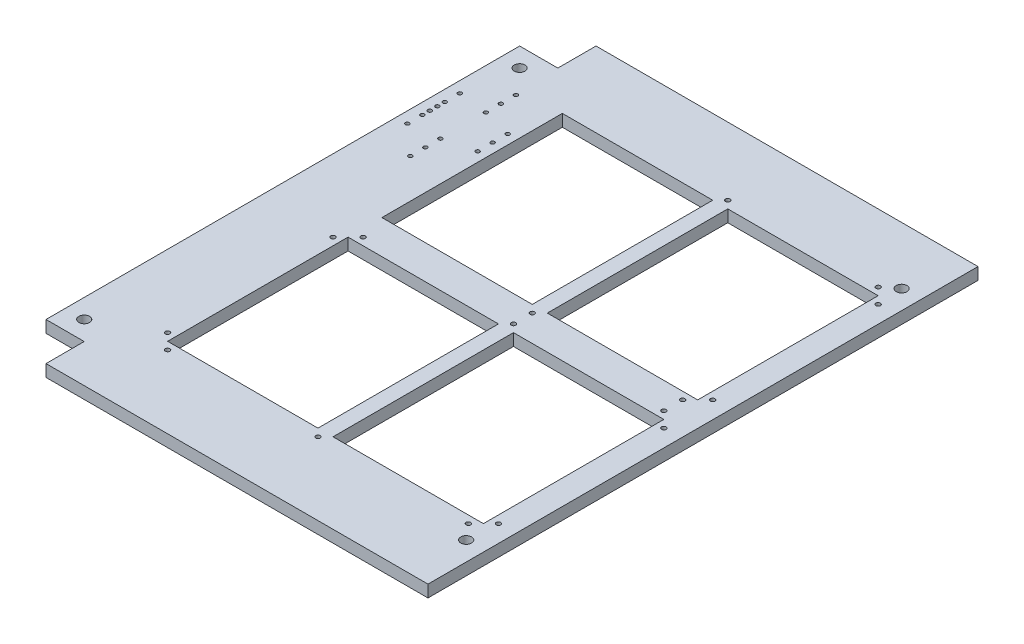
SolidWorks part; units mm, degrees
ref_plane "前视" through (0, 0, 0) normal (0, 0, 1) x (1, 0, 0)
ref_plane "上视" through (0, 0, 0) normal (0, 1, 0) x (1, 0, 0)
ref_plane "右视" through (0, 0, 0) normal (1, 0, 0) x (0, 0, -1)
sketch "Sketch1" plane through (0, 0, 0) normal (0, 1, 0) x (1, 0, 0)
  line L0 (-26.0564, 184.2499) -> (-26.0564, -181.5101) construction
  line L1 (-165.7564, 184.2499) -> (113.6436, 184.2499)
  line L2 (-165.7564, 184.2499) -> (-165.7564, -181.5101)
  line L3 (-165.7564, -181.5101) -> (113.6436, -181.5101)
  line L4 (113.6436, 184.2499) -> (113.6436, -181.5101)
  line L5 (-165.7564, 1.3699) -> (113.6436, 1.3699) construction
  line L6 (-140.3564, -156.1101) -> (-165.7564, -156.1101)
  line L7 (-140.3564, -156.1101) -> (-140.3564, -181.5101)
  line L12 (-140.3564, 158.8499) -> (-140.3564, 184.2499)
  line L13 (-140.3564, 158.8499) -> (-165.7564, 158.8499)
  point P4 (-140.3564, -156.1101)
  point P11 (-140.3564, 158.8499)
  dimension "D1" = 279.4
  dimension "D2" = 365.76
  dimension "D3" = 25.4
  dimension "D4" = 25.4
extrude "Boss-Extrude1" add sketch "Sketch1" along normal blind 8 contours L12 L13 L2 L6 L7 L3 L4 L1 region at (-24.4324, 0, -1.3699)
sketch "Sketch2" plane through (0, 8, 0) normal (0, 1, 0) x (1, 0, 0)
  line L0 (-140.3564, -156.1101) -> (-165.7564, -156.1101) construction
  line L1 (-165.7564, 1.3699) -> (113.6436, 1.3699) construction
  line L2 (-165.7564, 158.8499) -> (-165.7564, -156.1101) construction
  line L3 (113.6436, 184.2499) -> (113.6436, -181.5101) construction
  line L4 (-26.0564, 1.3699) -> (-26.0564, -181.5101) construction
  line L7 (-140.3564, -181.5101) -> (113.6436, -181.5101) construction
  circle A0 centre (-153.0564, -143.3901) radius 3.57
  circle A1 centre (100.9436, 146.1299) radius 3.57
  circle A2 centre (100.9436, -143.3901) radius 3.57
  circle A3 centre (-153.0564, 146.1299) radius 3.57
  point P0 (-153.0564, -143.3901)
  point P1 (-153.0564, -156.1101)
  dimension "D1" = 12.72
extrude "Cut-Extrude1" cut sketch "Sketch2" against normal through all
sketch "Sketch3" plane through (0, 8, 0) normal (0, 1, 0) x (1, 0, 0)
  line L0 (-158.4056, 91.6911) -> (-158.4056, 76.8011) construction
  line L2 (-119.0906, 84.2461) -> (-158.4056, 84.2461) construction
  line L3 (-140.3564, 184.2499) -> (113.6436, 184.2499) construction
  circle A0 centre (-158.4056, 101.6911) radius 1.3
  circle A1 centre (-158.4056, 91.6911) radius 1.3
  circle A2 centre (-158.4056, 86.8011) radius 1.3
  circle A3 centre (-158.4056, 76.8011) radius 1.3
  circle A4 centre (-138.7481, 69.1311) radius 1.3
  circle A5 centre (-138.7481, 59.1311) radius 1.3
  circle A6 centre (-119.0906, 84.2461) radius 1.3
  circle A7 centre (-138.7481, 109.3611) radius 1.3
  circle A8 centre (-119.0906, 94.2461) radius 1.3
  circle A9 centre (-138.7481, 119.3611) radius 1.3
  circle A10 centre (-158.4056, 111.6911) radius 1.3
  circle A11 centre (-158.4056, 96.8011) radius 1.3
  circle A12 centre (-138.7481, 79.1311) radius 1.3
  circle A13 centre (-119.0906, 104.2461) radius 1.3
  circle A14 centre (-138.7481, 129.3611) radius 1.3
  point P0 (-158.4056, 91.6911)
  point P1 (-158.4056, 76.8011)
  dimension "D4" = 3
  dimension "D1" = 14.89
  dimension "D2" = 100.0038
  dimension "D3" = 39.315
extrude "Cut-Extrude2" cut sketch "Sketch3" against normal through all
sketch "Sketch5" plane through (0, 8, 0) normal (0, 1, 0) x (1, 0, 0)
  line L0 (-112.7564, 14.2499) -> (-12.7564, 14.2499)
  line L1 (-112.7564, 134.2499) -> (-12.7564, 134.2499)
  line L2 (-112.7564, 134.2499) -> (-112.7564, -128.2501)
  line L3 (-12.7564, 134.2499) -> (-12.7564, -128.2501)
  line L4 (-165.7564, 158.8499) -> (-165.7564, -156.1101) construction
  line L5 (-112.7564, -8.2501) -> (-12.7564, -8.2501)
  line L6 (-112.7564, -128.2501) -> (-12.7564, -128.2501)
  line L7 (-140.3564, -181.5101) -> (113.6436, -181.5101) construction
  line L8 (-2.7564, 134.2499) -> (-2.7564, -128.2501)
  line L9 (-140.3564, 184.2499) -> (113.6436, 184.2499) construction
  line L10 (97.2436, 134.2499) -> (97.2436, -128.2501)
  line L11 (-2.7564, 134.2499) -> (97.2436, 134.2499)
  line L12 (-2.7564, 14.2499) -> (97.2436, 14.2499)
  line L13 (-2.7564, -8.2501) -> (97.2436, -8.2501)
  line L14 (-2.7564, -128.2501) -> (97.2436, -128.2501)
  dimension "D1" = 100
  dimension "D2" = 53
  dimension "D3" = 120
  dimension "D4" = 22.5
  dimension "D5" = 120
  dimension "D6" = 53.26
  dimension "D7" = 2
  dimension "D8" = 50
extrude "Cut-Extrude3" cut sketch "Sketch5" against normal through all contours L1 L0 | L6 L5 | L8 L12 L10 L11 | L8 L14 L10 L13 region at (-62.7564, 8, -74.2499) region at (-62.7564, 8, 68.2501) region at (47.2436, 8, -74.2499) region at (47.2436, 8, 68.2501)
sketch "Sketch6" plane through (0, 8, 0) normal (0, 1, 0) x (1, 0, 0)
  line L0 (-112.7564, -8.2501) -> (-112.7564, -128.2501) construction
  line L1 (-112.7564, -128.2501) -> (-12.7564, -128.2501) construction
  line L2 (-12.7564, -8.2501) -> (-12.7564, -128.2501) construction
  line L3 (-112.7564, -8.2501) -> (-12.7564, -8.2501) construction
  line L4 (-2.7564, 14.2499) -> (97.2436, 14.2499) construction
  line L5 (97.2436, -8.2501) -> (97.2436, -128.2501) construction
  line L6 (-2.7564, 134.2499) -> (97.2436, 134.2499) construction
  circle A0 centre (-117.7564, -123.2501) radius 1.5
  circle A1 centre (-7.7564, -133.2501) radius 1.5
  circle A2 centre (-107.7564, -133.2501) radius 1.5
  circle A3 centre (-107.7564, -3.2501) radius 1.5
  circle A4 centre (-117.7564, -13.2501) radius 1.5
  circle A5 centre (-7.7564, -3.2501) radius 1.5
  circle A6 centre (-7.7564, 9.2499) radius 1.5
  circle A7 centre (102.2436, -13.2501) radius 1.5
  circle A8 centre (92.2436, -3.2501) radius 1.5
  circle A9 centre (92.2436, 9.2499) radius 1.5
  circle A10 centre (102.2436, 19.2499) radius 1.5
  circle A11 centre (92.2436, -133.2501) radius 1.5
  circle A12 centre (102.2436, -123.2501) radius 1.5
  circle A13 centre (-7.7564, 139.2499) radius 1.5
  circle A14 centre (92.2436, 139.2499) radius 1.5
  circle A15 centre (102.2436, 129.2499) radius 1.5
  dimension "D3" = 3
  dimension "D6" = 3
  dimension "D1" = 5
  dimension "D2" = 5
  dimension "D4" = 5
  dimension "D5" = 5
  dimension "D7" = 5
  dimension "D8" = 5
  dimension "D9" = 5
  dimension "D10" = 5
  dimension "D11" = 5
  dimension "D12" = 5
  dimension "D13" = 5
  dimension "D14" = 5
  dimension "D15" = 5
extrude "Cut-Extrude4" cut sketch "Sketch6" against normal through all
